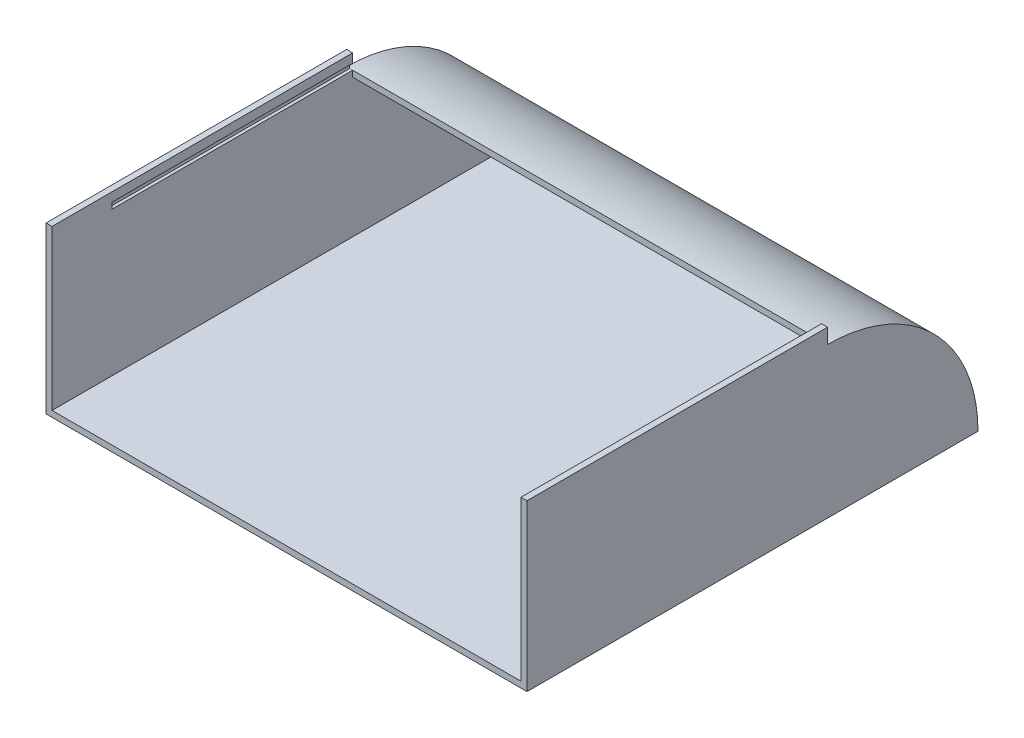
SolidWorks part; units mm, degrees
ref_plane "Front Plane" through (0, 0, 0) normal (0, 0, 1) x (1, 0, 0)
ref_plane "Top Plane" through (0, 0, 0) normal (0, 1, 0) x (1, 0, 0)
ref_plane "Right Plane" through (0, 0, 0) normal (1, 0, 0) x (0, 0, -1)
sketch "Sketch1" plane through (0, 0, 0) normal (1, 0, 0) x (0, 0, -1)
  line L1 (75, -25) -> (-75, -25)
  line L2 (75, -25) -> (75, 25)
  line L3 (75, 25) -> (-75, 25)
  line L4 (-75, -25) -> (-75, 25)
  line L5 (75, -25) -> (-75, 25) construction
  line L6 (75, 25) -> (-75, -25) construction
  point P0 (0, 0)
  dimension "D1" = 50
  dimension "D2" = 150
extrude "Boss-Extrude1" add sketch "Sketch1" against normal blind 160
fillet "Fillet2" radius 50 1 edges at (-80, 25, -75)
sketch "Sketch17" plane through (0, 25, 0) normal (0, 1, 0) x (1, 0, 0)
  line L0 (-80, 25) -> (-158, 25)
  line L1 (0, 25) -> (-160, 25) construction
  line L2 (-80, 25) -> (-2, 25)
  line L7 (-158, 25) -> (-158, -75)
  line L8 (-160, -75) -> (0, -75) construction
  line L9 (-2, 25) -> (-2, -75)
  line L10 (-2, -75) -> (-158, -75)
shell "Shell1" thickness 2 removed face at (-80, 0, 75)
extrude "Cut-Extrude1" cut sketch "Sketch17" against normal blind 2
sketch "Sketch20" plane through (0, 25, 0) normal (0, 1, 0) x (1, 0, 0)
  line L1 (-160, 25) -> (-158, 25)
  line L2 (-160, 25) -> (-160, -75)
  line L3 (-160, -75) -> (-158, -75)
  line L4 (-158, 25) -> (-158, -75)
  line L5 (-2, 25) -> (0, 25)
  line L6 (-2, 25) -> (-2, -75)
  line L7 (-2, -75) -> (0, -75)
  line L8 (0, 25) -> (0, -75)
extrude "Boss-Extrude2" add sketch "Sketch20" along normal blind 5
sketch "Sketch21" plane through (-158, 0, 0) normal (1, 0, 0) x (0, 0, -1)
  line L1 (25, 25) -> (-55, 25)
  line L2 (25, 25) -> (25, 27)
  line L3 (25, 27) -> (-55, 27)
  line L4 (-55, 25) -> (-55, 27)
  dimension "D1" = 80
  dimension "D2" = 2
extrude "Cut-Extrude2" cut sketch "Sketch21" against normal blind 1
sketch "Sketch22" plane through (-2, 0, 0) normal (-1, 0, 0) x (0, 0, 1)
  line L1 (-25, 25) -> (55, 25)
  line L2 (-25, 25) -> (-25, 27)
  line L3 (-25, 27) -> (55, 27)
  line L4 (55, 25) -> (55, 27)
  dimension "D1" = 80
  dimension "D2" = 2
extrude "Cut-Extrude3" cut sketch "Sketch22" against normal blind 1
sketch "Sketch24" plane through (0, 25, 0) normal (0, 1, 0) x (1, 0, 0)
  line L0 (-2, 25) -> (-2, -55) construction
  line L1 (-1, -55) -> (-2, -55) construction
  circle A0 centre (-1.5, -50) radius 0.5
  dimension "D1" = 0.5
  dimension "D2" = 5
sketch "Sketch25" plane through (0, 25, 0) normal (0, 1, 0) x (1, 0, 0)
  line L0 (-1.5, -50) -> (-1.4753, -50.4994)
  line L1 (-1.5, -50) -> (-1.5247, -49.5006)
  line L2 (-2, -55) -> (-2, 25) construction
  arc A0 (-1.4753, -50.4994) -> (-1.5247, -49.5006) centre (-1.5, -50) cw
  dimension "D1" = 0.5
  dimension "D2" = 0.5
revolve "Cut-Revolve1" cut sketch "Sketch25" angle 360 about L1 region at (-1.7119, 25, 50.0105)
